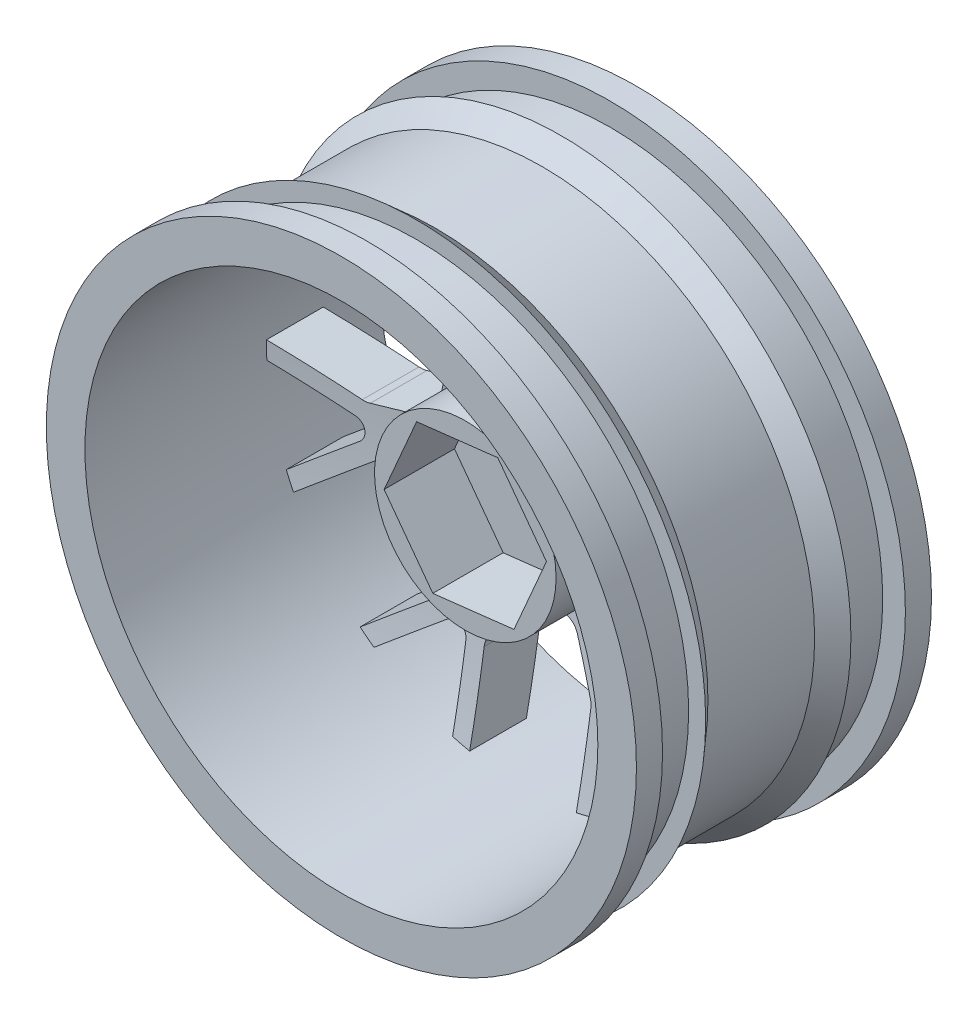
SolidWorks part; units mm, degrees
ref_plane "Front" through (0, 0, 0) normal (0, 0, 1) x (1, 0, 0)
ref_plane "Top" through (0, 0, 0) normal (0, 1, 0) x (1, 0, 0)
ref_plane "Right" through (0, 0, 0) normal (1, 0, 0) x (0, 0, -1)
sketch "Sketch4" plane through (0, 0, 0) normal (1, 0, 0) x (0, 0, -1)
  line L0 (0, 0) -> (26, 0) construction
  line L1 (0, 22.6) -> (0, 26)
  line L2 (0, 26) -> (2.3, 26)
  line L3 (2.3, 26) -> (2.3, 24)
  line L4 (2.3, 24) -> (6.6, 24)
  line L5 (6.6, 24) -> (6.6, 25.5)
  line L6 (6.6, 25.5) -> (8.3, 24)
  line L7 (8.3, 24) -> (17.7, 24)
  line L8 (13, 24) -> (13, 26) construction
  line L9 (0, 22.6) -> (26, 22.6)
  line L11 (26, 22.6) -> (26, 26)
  line L12 (26, 26) -> (23.7, 26)
  line L13 (23.7, 26) -> (23.7, 24)
  line L14 (23.7, 24) -> (19.4, 24)
  line L15 (19.4, 24) -> (19.4, 25.5)
  line L16 (19.4, 25.5) -> (17.7, 24)
  dimension "D1" = 3.4
  dimension "D2" = 2.3
  dimension "D3" = 4.3
  dimension "D4" = 4.7
  dimension "D5" = 2
  dimension "D6" = 26
  dimension "D7" = 1.7
  dimension "D8" = 1.5
revolve "Revolve1" add sketch "Sketch4" angle 360 about L0
sketch "Sketch6" plane through (0, 0, 0) normal (1, 0, 0) x (0, 0, -1)
  line L0 (0, 0) -> (26, 0) construction
  line L1 (26, -22.6) -> (26, 22.6) construction
  line L2 (0, 26) -> (26, 26) construction
  line L3 (26, -26) -> (26, 26) construction
  line L4 (13, 0) -> (13, 26) construction
  line L5 (18.5, -22.6) -> (18.5, -15.9253) construction
  line L6 (26, -26) -> (0, -26) construction
  line L7 (23.7, 24) -> (23.7, -24) construction
  line L8 (23.7, 0) -> (18.7, 0)
  line L9 (13, 0) -> (13, -26) construction
  line L10 (16, -22.6) -> (21, -22.6)
  spline S0 degree 2 poles (21, -22.6) (23.3323, -11.4217) (23.7, 0) knots 0 0 0 1 1 1
  spline S1 degree 2 poles (16, -22.6) (18.3323, -11.4217) (18.7, 0) knots 0 0 0 1 1 1
  point P22 (23.7, 0)
  point P30 (18.7, 0)
  dimension "D1" = 3.4
  dimension "D2" = 5
  dimension "D3" = 5
  dimension "D4" = 1.7
  dimension "D5" = 10.1
  dimension "D6" = 12.5
  dimension "D7" = 1.7
  dimension "D8" = 5
revolve "Revolve2" add sketch "Sketch6" angle 360 about L0
sketch "Sketch7" plane through (0, 0, -26) normal (0, 0, -1) x (-1, 0, 0)
  line L0 (1.5212, -9.45) -> (-1.5212, -9.45)
  line L1 (-4.7, -14.7654) -> (-4.7, -22.1059)
  line L2 (0, -9.45) -> (0, -13.85) construction
  line L3 (-2.8942, -10.3459) -> (-4.573, -14.1613)
  line L4 (2.8942, -10.3459) -> (4.573, -14.1613)
  line L5 (4.7, -14.7654) -> (4.7, -22.1059)
  line L6 (-8.6137, -12.8807) -> (-14.3527, -17.4574)
  line L7 (-6.2842, -8.7133) -> (-8.2205, -12.4047)
  line L8 (-6.4398, -7.0813) -> (-8.3368, -4.7026)
  line L9 (-9.8932, -4.1878) -> (-13.923, -5.2541)
  line L10 (-14.4745, -5.5315) -> (-20.2135, -10.1082)
  line L11 (-15.4411, -1.2965) -> (-22.5975, 0.3369)
  line L12 (-10.7305, -0.5195) -> (-14.8238, -1.3071)
  line L13 (-9.5516, 0.6197) -> (-8.8746, 3.5859)
  line L14 (-9.4425, 5.1238) -> (-12.7887, 7.6095)
  line L15 (-13.3494, 7.8678) -> (-20.5058, 9.5012)
  line L16 (-10.641, 11.2639) -> (-13.8259, 17.8775)
  line L17 (-7.0965, 8.0656) -> (-10.2645, 10.7748)
  line L18 (-5.4708, 7.8541) -> (-2.7296, 9.1742)
  line L19 (-1.8813, 10.5771) -> (-2.0243, 14.743)
  line L20 (-2.1719, 15.3424) -> (-5.3568, 21.956)
  line L21 (2.1719, 15.3424) -> (5.3568, 21.956)
  line L22 (1.8813, 10.5771) -> (2.0243, 14.743)
  line L23 (2.7296, 9.1742) -> (5.4708, 7.8541)
  line L24 (7.0965, 8.0656) -> (10.2645, 10.7748)
  line L25 (10.641, 11.2639) -> (13.8259, 17.8775)
  line L26 (13.3494, 7.8678) -> (20.5058, 9.5012)
  line L27 (9.4425, 5.1238) -> (12.7887, 7.6095)
  line L28 (8.8746, 3.5859) -> (9.5516, 0.6197)
  line L29 (10.7305, -0.5195) -> (14.8238, -1.3071)
  line L30 (15.4411, -1.2965) -> (22.5975, 0.3369)
  line L31 (14.4745, -5.5315) -> (20.2135, -10.1082)
  line L32 (9.8932, -4.1878) -> (13.923, -5.2541)
  line L33 (8.3368, -4.7026) -> (6.4398, -7.0813)
  line L34 (6.2842, -8.7133) -> (8.2205, -12.4047)
  line L35 (8.6137, -12.8807) -> (14.3527, -17.4574)
  line L36 (6.2, -21.7329) -> (6.2, -14.951)
  line L37 (7.8235, -14.1691) -> (13.1258, -18.3976)
  line L38 (-13.1258, -18.3976) -> (-7.8235, -14.1691)
  line L39 (-6.2, -14.951) -> (-6.2, -21.7329)
  line L40 (-22.5677, -1.2085) -> (-15.9557, -2.7177)
  line L41 (-15.5548, -4.4744) -> (-20.8571, -8.7029)
  line L42 (-15.0156, 16.8906) -> (-12.073, 10.7803)
  line L43 (-13.1965, 9.3715) -> (-19.8084, 10.8806)
  line L44 (3.8436, 22.2708) -> (0.901, 16.1604)
  line L45 (-0.901, 16.1604) -> (-3.8436, 22.2708)
  line L46 (19.8084, 10.8806) -> (13.1965, 9.3715)
  line L47 (12.073, 10.7803) -> (15.0156, 16.8906)
  line L48 (20.8571, -8.7029) -> (15.5548, -4.4744)
  line L49 (15.9557, -2.7177) -> (22.5677, -1.2085)
  circle A0 centre (0, 0) radius 2.25
  circle A1 centre (0, 0) radius 22.6 construction
  arc A2 (-4.7, -22.1059) -> (4.7, -22.1059) centre (0, 0) ccw
  arc A3 (-20.2135, -10.1082) -> (-14.3527, -17.4574) centre (0, 0) ccw
  arc A4 (-20.5058, 9.5012) -> (-22.5975, 0.3369) centre (0, 0) ccw
  arc A5 (-5.3568, 21.956) -> (-13.8259, 17.8775) centre (0, 0) ccw
  arc A6 (13.8259, 17.8775) -> (5.3568, 21.956) centre (0, 0) ccw
  arc A7 (22.5975, 0.3369) -> (20.5058, 9.5012) centre (0, 0) ccw
  arc A8 (14.3527, -17.4574) -> (20.2135, -10.1082) centre (0, 0) ccw
  circle A9 centre (0, 0) radius 22.6 construction
  arc A10 (-4.7, -22.1059) -> (4.7, -22.1059) centre (0, 0) ccw
  arc A11 (6.2, -14.951) -> (7.8235, -14.1691) centre (7.2, -14.951) cw
  arc A12 (22.5975, 0.3369) -> (20.5058, 9.5012) centre (0, 0) ccw
  arc A13 (13.8259, 17.8775) -> (5.3568, 21.956) centre (0, 0) ccw
  arc A14 (-5.3568, 21.956) -> (-13.8259, 17.8775) centre (0, 0) ccw
  arc A15 (-20.5058, 9.5012) -> (-22.5975, 0.3369) centre (0, 0) ccw
  arc A16 (-20.2135, -10.1082) -> (-14.3527, -17.4574) centre (0, 0) ccw
  arc A17 (6.2, -21.7329) -> (13.1258, -18.3976) centre (0, 0) ccw
  arc A18 (14.3527, -17.4574) -> (20.2135, -10.1082) centre (0, 0) ccw
  arc A19 (-7.8235, -14.1691) -> (-6.2, -14.951) centre (-7.2, -14.951) cw
  arc A20 (-13.1258, -18.3976) -> (-6.2, -21.7329) centre (0, 0) ccw
  arc A21 (-15.9557, -2.7177) -> (-15.5548, -4.4744) centre (-16.1783, -3.6926) cw
  arc A22 (-22.5677, -1.2085) -> (-20.8571, -8.7029) centre (0, 0) ccw
  arc A23 (-12.073, 10.7803) -> (-13.1965, 9.3715) centre (-12.974, 10.3464) cw
  arc A24 (-15.0156, 16.8906) -> (-19.8084, 10.8806) centre (0, 0) ccw
  arc A25 (0.901, 16.1604) -> (-0.901, 16.1604) centre (0, 16.5943) cw
  arc A26 (3.8436, 22.2708) -> (-3.8436, 22.2708) centre (0, 0) ccw
  arc A27 (13.1965, 9.3715) -> (12.073, 10.7803) centre (12.974, 10.3464) cw
  arc A28 (19.8084, 10.8806) -> (15.0156, 16.8906) centre (0, 0) ccw
  arc A29 (15.5548, -4.4744) -> (15.9557, -2.7177) centre (16.1783, -3.6926) cw
  arc A30 (20.8571, -8.7029) -> (22.5677, -1.2085) centre (0, 0) ccw
  arc A31 (8.2205, -12.4047) -> (8.6137, -12.8807) centre (9.5489, -11.7079) ccw
  arc A32 (6.4398, -7.0813) -> (6.2842, -8.7133) centre (7.6126, -8.0166) ccw
  arc A33 (9.8932, -4.1878) -> (8.3368, -4.7026) centre (9.5095, -5.6379) ccw
  arc A34 (14.4745, -5.5315) -> (13.923, -5.2541) centre (13.5392, -6.7042) ccw
  arc A35 (14.8238, -1.3071) -> (15.4411, -1.2965) centre (15.1073, 0.1658) ccw
  arc A36 (9.5516, 0.6197) -> (10.7305, -0.5195) centre (11.014, 0.9535) ccw
  arc A37 (9.4425, 5.1238) -> (8.8746, 3.5859) centre (10.337, 3.9197) ccw
  arc A38 (13.3494, 7.8678) -> (12.7887, 7.6095) centre (13.6831, 6.4054) ccw
  arc A39 (1.8813, 10.5771) -> (2.7296, 9.1742) centre (3.3805, 10.5256) ccw
  arc A40 (5.4708, 7.8541) -> (7.0965, 8.0656) centre (6.1216, 9.2056) ccw
  arc A41 (10.2645, 10.7748) -> (10.641, 11.2639) centre (9.2896, 11.9147) ccw
  arc A42 (2.1719, 15.3424) -> (2.0243, 14.743) centre (3.5234, 14.6916) ccw
  arc A43 (-10.641, 11.2639) -> (-10.2645, 10.7748) centre (-9.2896, 11.9147) ccw
  arc A44 (-7.0965, 8.0656) -> (-5.4708, 7.8541) centre (-6.1216, 9.2056) ccw
  arc A45 (-2.7296, 9.1742) -> (-1.8813, 10.5771) centre (-3.3805, 10.5256) ccw
  arc A46 (-2.0243, 14.743) -> (-2.1719, 15.3424) centre (-3.5234, 14.6916) ccw
  arc A47 (-12.7887, 7.6095) -> (-13.3494, 7.8678) centre (-13.6831, 6.4054) ccw
  arc A48 (-8.8746, 3.5859) -> (-9.4425, 5.1238) centre (-10.337, 3.9197) ccw
  arc A49 (-15.4411, -1.2965) -> (-14.8238, -1.3071) centre (-15.1073, 0.1658) ccw
  arc A50 (-10.7305, -0.5195) -> (-9.5516, 0.6197) centre (-11.014, 0.9535) ccw
  arc A51 (-6.2842, -8.7133) -> (-6.4398, -7.0813) centre (-7.6126, -8.0166) ccw
  arc A52 (-8.3368, -4.7026) -> (-9.8932, -4.1878) centre (-9.5095, -5.6379) ccw
  arc A53 (-13.923, -5.2541) -> (-14.4745, -5.5315) centre (-13.5392, -6.7042) ccw
  arc A54 (-8.6137, -12.8807) -> (-8.2205, -12.4047) centre (-9.5489, -11.7079) ccw
  arc A55 (-4.7, -14.7654) -> (-4.573, -14.1613) centre (-3.2, -14.7654) cw
  arc A56 (4.573, -14.1613) -> (4.7, -14.7654) centre (3.2, -14.7654) cw
  arc A57 (-1.5212, -9.45) -> (-2.8942, -10.3459) centre (-1.5212, -10.95) ccw
  arc A58 (1.5212, -9.45) -> (2.8942, -10.3459) centre (1.5212, -10.95) cw
  point P3 (-2.25, 0)
  point P4 (0, 2.25)
  point P5 (2.25, 0)
  point P6 (0, -2.25)
  point P10 (0, -9.45)
  point P141 (-4.7, -14.45)
  point P144 (4.7, -14.45)
  point P147 (-2.5, -9.45)
  point P150 (2.5, -9.45)
  circle M63 centre (0, 0) radius 22.6
  dimension "D1" = 4.5
  dimension "D9" = 1
  dimension "D11" = 1.5
  dimension "D2" = 5
  dimension "D3" = 7.2
  dimension "D4" = 2.2
  dimension "D5" = 5
  dimension "D7" = 1.5
  dimension "D8" = 1.5
  dimension "D6" = 7
  dimension "D10" = 7
extrude "Cut-Extrude1" cut sketch "Sketch7" against normal through all both and the other way through all contours L31 A34 L32 A33 L33 A32 L34 A31 L35 M63 | A11 L36 L37 M63 | A58 L0 A57 L3 A55 L1 L5 A56 L4 M63 | A19 L38 L39 M63 | L6 A54 L7 A51 L8 A52 L9 A53 L10 M63 | A21 L40 L41 M63 | L12 A50 L13 A48 L14 A47 L15 L11 A49 M63 | A23 L42 L43 M63 | L19 A46 L20 L16 A43 L17 A44 L18 A45 M63 | A25 L44 L45 M63 | L21 A42 L22 A39 L23 A40 L24 A41 L25 M63 | A27 L46 L47 M63 | L26 A38 L27 A37 L28 A36 L29 A35 L30 M63 | A29 L48 L49 M63 region at (0, -16.4427, -26) region at (-8.6314, -17.9234, -26) region at (8.6314, -17.9234, -26) region at (-12.8554, -10.2518, -26) region at (12.8554, -10.2518, -26) region at (-19.3947, -4.4267, -26) region at (19.3947, -4.4267, -26) region at (16.0304, 3.6588, -26) region at (-16.0304, 3.6588, -26) region at (15.5533, 12.4034, -26) region at (-15.5533, 12.4034, -26) region at (7.1342, 14.8143, -26) region at (-7.1342, 14.8143, -26) region at (0, 19.8934, -26)
ref_plane "Plane1" through (0, 0, -23.7) normal (0, 0, -1) x (-1, 0, 0)
sketch "Sketch8" plane through (0, 0, -23.7) normal (0, 0, -1) x (-1, 0, 0)
  circle A0 centre (0, 0) radius 8
  dimension "D1" = 16
extrude "Cut-Extrude2" cut sketch "Sketch8" against normal blind 3
sketch "Sketch9" plane through (0, 0, -20.7) normal (0, 0, -1) x (-1, 0, 0)
  line L1 (4.2904, 5.7821) -> (-2.8623, 6.6066)
  line L2 (-2.8623, 6.6066) -> (-7.1526, 0.8245)
  line L3 (-7.1526, 0.8245) -> (-4.2904, -5.7821)
  line L4 (-4.2904, -5.7821) -> (2.8623, -6.6066)
  line L5 (2.8623, -6.6066) -> (7.1526, -0.8245)
  line L6 (7.1526, -0.8245) -> (4.2904, 5.7821)
  circle A0 centre (0, 0) radius 6.2354 construction
  circle A1 centre (0, 0) radius 8
  circle A4 centre (0, 0) radius 8
  dimension "D2" = 7.2
  dimension "D1" = 0
extrude "Boss-Extrude1" add sketch "Sketch9" against normal blind 8.6291
sketch "Sketch10" plane through (0, 0, -20.7) normal (0, 0, -1) x (-1, 0, 0)
  circle A0 centre (0, 0) radius 8 construction
  circle A1 centre (0, 0) radius 8
  circle A2 centre (0, 0) radius 6
  circle A3 centre (0, 0) radius 6 construction
  dimension "D1" = 2
extrude "Boss-Extrude2" add sketch "Sketch10" along normal blind 0.8
sketch "Sketch11" plane through (0, 0, -21.5) normal (0, 0, -1) x (-1, 0, 0)
  line L0 (0, 0) -> (8, 0) construction
  circle A0 centre (0, 0) radius 8 construction
  arc A5 (5.8462, -1.35) -> (5.8462, 1.35) centre (6.5, 0) ccw
  circle A14 centre (0, 0) radius 6 construction
  arc A15 (5.8462, -1.35) -> (5.8462, 1.35) centre (0, 0) ccw
  arc A16 (0.5226, -5.9772) -> (3.0905, -5.1429) centre (0, 0) ccw
  arc A17 (0.5226, -5.9772) -> (3.0905, -5.1429) centre (2.0086, -6.1819) ccw
  arc A18 (-5.5231, -2.3441) -> (-3.9361, -4.5285) centre (0, 0) ccw
  arc A19 (-5.5231, -2.3441) -> (-3.9361, -4.5285) centre (-5.2586, -3.8206) ccw
  arc A20 (-3.9361, 4.5285) -> (-5.5231, 2.3441) centre (0, 0) ccw
  arc A21 (-3.9361, 4.5285) -> (-5.5231, 2.3441) centre (-5.2586, 3.8206) ccw
  arc A22 (3.0905, 5.1429) -> (0.5226, 5.9772) centre (0, 0) ccw
  arc A23 (3.0905, 5.1429) -> (0.5226, 5.9772) centre (2.0086, 6.1819) ccw
  dimension "D1" = 3
  dimension "D2" = 5
extrude "Cut-Extrude3" cut sketch "Sketch11" against normal up to surface (0.8 mm away) up to face at (-6, 0, -20.7)
sketch "Sketch13" plane through (0, 0, -20.7) normal (0, 0, -1) x (-1, 0, 0)
  circle A0 centre (0, 0) radius 2.25
  dimension "D1" = 4.5
extrude "Cut-Extrude4" cut sketch "Sketch13" against normal through all both and the other way through all
ref_plane "Plane2" through (0, 0, -18.2709) normal (0, 0, 1) x (1, 0, 0)
sketch "Sketch14" plane through (0, 0, -18.2709) normal (0, 0, 1) x (1, 0, 0)
  line L6 (2.8623, 6.6066) -> (-4.2904, 5.7821)
  line L7 (-4.2904, 5.7821) -> (-7.1526, -0.8245)
  line L8 (-7.1526, -0.8245) -> (-2.8623, -6.6066)
  line L9 (-2.8623, -6.6066) -> (4.2904, -5.7821)
  line L10 (4.2904, -5.7821) -> (7.1526, 0.8245)
  line L11 (7.1526, 0.8245) -> (2.8623, 6.6066)
  line L12 (2.8623, 6.6066) -> (-4.2904, 5.7821)
  line L13 (-4.2904, 5.7821) -> (-7.1526, -0.8245)
  line L14 (-7.1526, -0.8245) -> (-2.8623, -6.6066)
  line L15 (-2.8623, -6.6066) -> (4.2904, -5.7821)
  line L16 (4.2904, -5.7821) -> (7.1526, 0.8245)
  line L17 (7.1526, 0.8245) -> (2.8623, 6.6066)
  circle A0 centre (0, 0) radius 2.25 construction
  circle A1 centre (0, 0) radius 2.25
  dimension "D1" = 0
extrude "Boss-Extrude3" add sketch "Sketch14" against normal up to surface up to face at (0, -2.25, -18.6084)
sketch "Sketch15" plane through (0, 0, -18.2709) normal (0, 0, 1) x (1, 0, 0)
  line L6 (-4.2904, 5.7821) -> (-7.1526, -0.8245)
  line L7 (-7.1526, -0.8245) -> (-2.8623, -6.6066)
  line L8 (-2.8623, -6.6066) -> (4.2904, -5.7821)
  line L9 (4.2904, -5.7821) -> (7.1526, 0.8245)
  line L10 (7.1526, 0.8245) -> (2.8623, 6.6066)
  line L11 (2.8623, 6.6066) -> (-4.2904, 5.7821)
  line L12 (-4.2904, 5.7821) -> (-7.1526, -0.8245)
  line L13 (-7.1526, -0.8245) -> (-2.8623, -6.6066)
  line L14 (-2.8623, -6.6066) -> (4.2904, -5.7821)
  line L15 (4.2904, -5.7821) -> (7.1526, 0.8245)
  line L16 (7.1526, 0.8245) -> (2.8623, 6.6066)
  line L17 (2.8623, 6.6066) -> (-4.2904, 5.7821)
  circle A0 centre (0, 0) radius 2.25 construction
  circle A1 centre (0, 0) radius 2.25
  dimension "D1" = 0
extrude "Boss-Extrude4" add sketch "Sketch15" along normal blind 1.1509
sketch "Sketch16" plane through (0, 0, -12.0709) normal (0, 0, 1) x (1, 0, 0)
  line L6 (2.8623, 6.6066) -> (-4.2904, 5.7821)
  line L7 (-4.2904, 5.7821) -> (-7.1526, -0.8245)
  line L8 (-7.1526, -0.8245) -> (-2.8623, -6.6066)
  line L9 (-2.8623, -6.6066) -> (4.2904, -5.7821)
  line L10 (4.2904, -5.7821) -> (7.1526, 0.8245)
  line L11 (7.1526, 0.8245) -> (2.8623, 6.6066)
  line L12 (2.8623, 6.6066) -> (-4.2904, 5.7821)
  line L13 (-4.2904, 5.7821) -> (-7.1526, -0.8245)
  line L14 (-7.1526, -0.8245) -> (-2.8623, -6.6066)
  line L15 (-2.8623, -6.6066) -> (4.2904, -5.7821)
  line L16 (4.2904, -5.7821) -> (7.1526, 0.8245)
  line L17 (7.1526, 0.8245) -> (2.8623, 6.6066)
  circle A1 centre (0, 0) radius 2.25 construction
  circle A2 centre (0, 0) radius 8
  circle A4 centre (0, 0) radius 8
  circle A5 centre (0, 0) radius 2.25
  line M9 (-2.8623, -6.6066) -> (-7.1526, -0.8245)
  line M10 (-7.1526, -0.8245) -> (-4.2904, 5.7821)
  line M11 (-4.2904, 5.7821) -> (2.8623, 6.6066)
  line M12 (2.8623, 6.6066) -> (7.1526, 0.8245)
  line M13 (7.1526, 0.8245) -> (4.2904, -5.7821)
  line M14 (4.2904, -5.7821) -> (-2.8623, -6.6066)
  circle M15 centre (0, 0) radius 8
  dimension "D1" = 0
  dimension "D2" = 0
extrude "Boss-Extrude5" add sketch "Sketch16" along normal blind 1.1509 contours M15 M14 M9 M10 M11 M12 M13 region at (-7.7737, 0, -12.0709)
